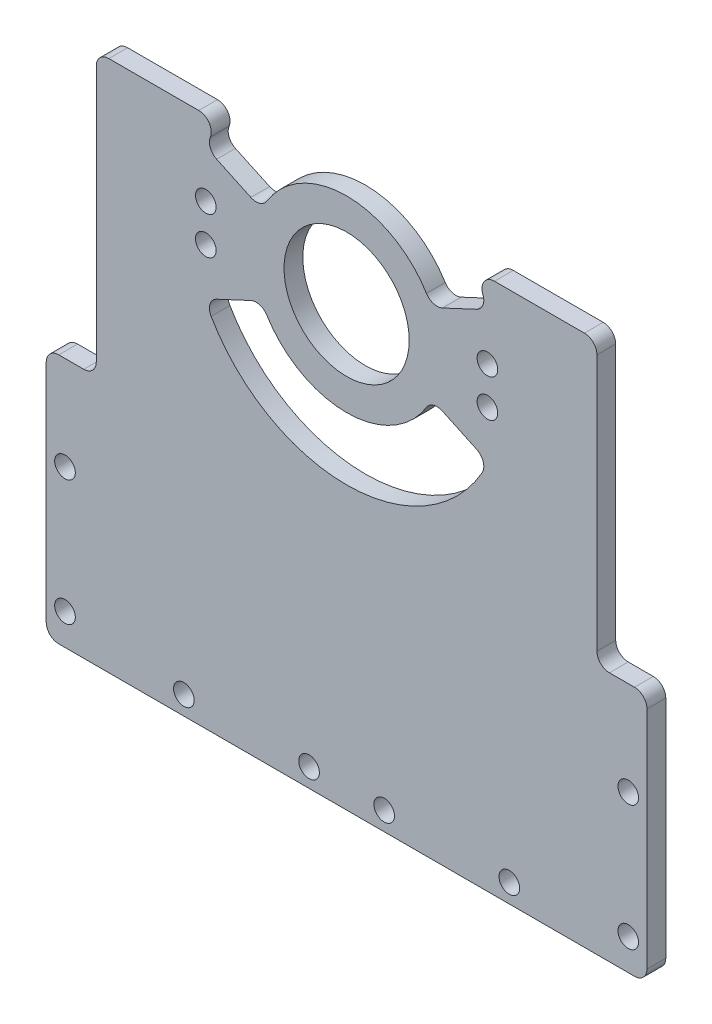
SolidWorks part; units mm, degrees
material "玻纤板"
ref_plane "前视基准面" through (0, 0, 0) normal (0, 0, 1) x (1, 0, 0)
ref_plane "上视基准面" through (0, 0, 0) normal (0, 1, 0) x (1, 0, 0)
ref_plane "右视基准面" through (0, 0, 0) normal (1, 0, 0) x (0, 0, -1)
other "Configuration Table"
sketch "草图1" plane through (0, 0, 0) normal (0, 0, 1) x (1, 0, 0)
  line L0 (0, 27.5) -> (0, -41.2576) construction
  line L1 (-40, 42.5) -> (40, 42.5)
  line L2 (-40, 42.5) -> (-40, -42.5)
  line L3 (-40, -42.5) -> (40, -42.5)
  line L4 (40, 42.5) -> (40, -42.5)
  line L5 (-40, 42.5) -> (40, -42.5) construction
  line L6 (-40, -42.5) -> (40, 42.5) construction
  line L7 (0, 27.5) -> (-56.2389, 27.5) construction
  circle A0 centre (0, 27.5) radius 10
  circle A1 centre (-6, -39.5) radius 1.65
  circle A2 centre (-26, -39.5) radius 1.65
  circle A3 centre (26, -39.5) radius 1.65
  circle A4 centre (6, -39.5) radius 1.65
  circle A5 centre (-22.5, 30.5) radius 1.65
  circle A6 centre (-22.5, 24.5) radius 1.65
  circle A7 centre (22.5, 30.5) radius 1.65
  circle A8 centre (22.5, 24.5) radius 1.65
  point P25 (0, 0)
  dimension "D1" = 20
  dimension "D2" = 3
  dimension "D3" = 3.3
  dimension "D4" = 20
  dimension "D5" = 12
  dimension "D8" = 3.3
  dimension "D9" = 45
  dimension "D10" = 70
  dimension "D6" = 80
  dimension "D7" = 6
  dimension "D11" = 85
extrude "凸台-拉伸1" add sketch "草图1" along normal blind 3
sketch "草图2" plane through (0, 0, 3) normal (0, 0, 1) x (1, 0, 0)
  line L0 (0, 27.5) -> (61.7399, 27.5) construction
  line L1 (22.6577, 16.9345) -> (13.5946, 21.1607)
  line L2 (0, 0) -> (0, 47.0881) construction
  line L3 (-22.6577, 16.9345) -> (-13.5946, 21.1607)
  line L4 (-22.6577, 38.0655) -> (-13.5946, 33.8393)
  line L5 (22.6577, 38.0655) -> (13.5946, 33.8393)
  arc A0 (-13.5946, 21.1607) -> (13.5946, 21.1607) centre (0, 27.5) ccw
  arc A1 (-22.6577, 16.9345) -> (22.6577, 16.9345) centre (0, 27.5) ccw
  arc A2 (-22.6577, 38.0655) -> (22.6577, 38.0655) centre (0, 27.5) cw
  arc A3 (-13.5946, 33.8393) -> (13.5946, 33.8393) centre (0, 27.5) cw
  dimension "D1" = 15
  dimension "D2" = 25
  dimension "D3" = 130
extrude "切除-拉伸1" cut sketch "草图2" against normal through all
sketch "草图3" plane through (0, 0, 3) normal (0, 0, 1) x (1, 0, 0)
  line L0 (0, -42.5) -> (0, 62.8928) construction
  line L1 (40, -42.5) -> (48, -42.5)
  line L2 (40, -42.5) -> (40, -2.5)
  line L3 (40, -2.5) -> (48, -2.5)
  line L4 (48, -42.5) -> (48, -2.5)
  line L5 (-40, -42.5) -> (40, -42.5) construction
  line L6 (-48, -42.5) -> (-48, -2.5)
  line L7 (-40, -2.5) -> (-48, -2.5)
  line L8 (-40, -42.5) -> (-40, -2.5)
  line L9 (-40, -42.5) -> (-48, -42.5)
  dimension "D1" = 8
  dimension "D2" = 40
extrude "凸台-拉伸2" add sketch "草图3" against normal blind 3
sketch "草图4" plane through (0, 0, 3) normal (0, 0, 1) x (1, 0, 0)
  line L0 (-48, -42.5) -> (48, -42.5) construction
  line L1 (48, -42.5) -> (48, -2.5) construction
  line L2 (0, -42.5) -> (0, 57.9613) construction
  circle A0 centre (45, -37.5) radius 1.65
  circle A1 centre (45, -17.5) radius 1.65
  circle A2 centre (-45, -17.5) radius 1.65
  circle A3 centre (-45, -37.5) radius 1.65
  dimension "D1" = 3.3
  dimension "D4" = 20
  dimension "D2" = 5
  dimension "D3" = 3
extrude "切除-拉伸2" cut sketch "草图4" against normal through all
fillet "圆角1" radius 2 12 edges at (-40, 42.5, 1.5) (22.6577, 16.9345, 1.5) (-22.6577, 16.9345, 1.5) (13.5946, 21.1607, 1.5) (-13.5946, 21.1607, 1.5) (-22.6577, 38.0655, 1.5) (-13.5946, 33.8393, 1.5) (13.5946, 33.8393, 1.5) (22.6577, 38.0655, 1.5) (-48, -2.5, 1.5) (40, -2.5, 1.5) (48, -2.5, 1.5)
fillet "圆角2" radius 2 6 edges at (-20, 42.5, 1.5) (40, 42.5, 1.5) (-48, -42.5, 1.5) (48, -42.5, 1.5) (20, 42.5, 1.5) (-40, -2.5, 1.5)
